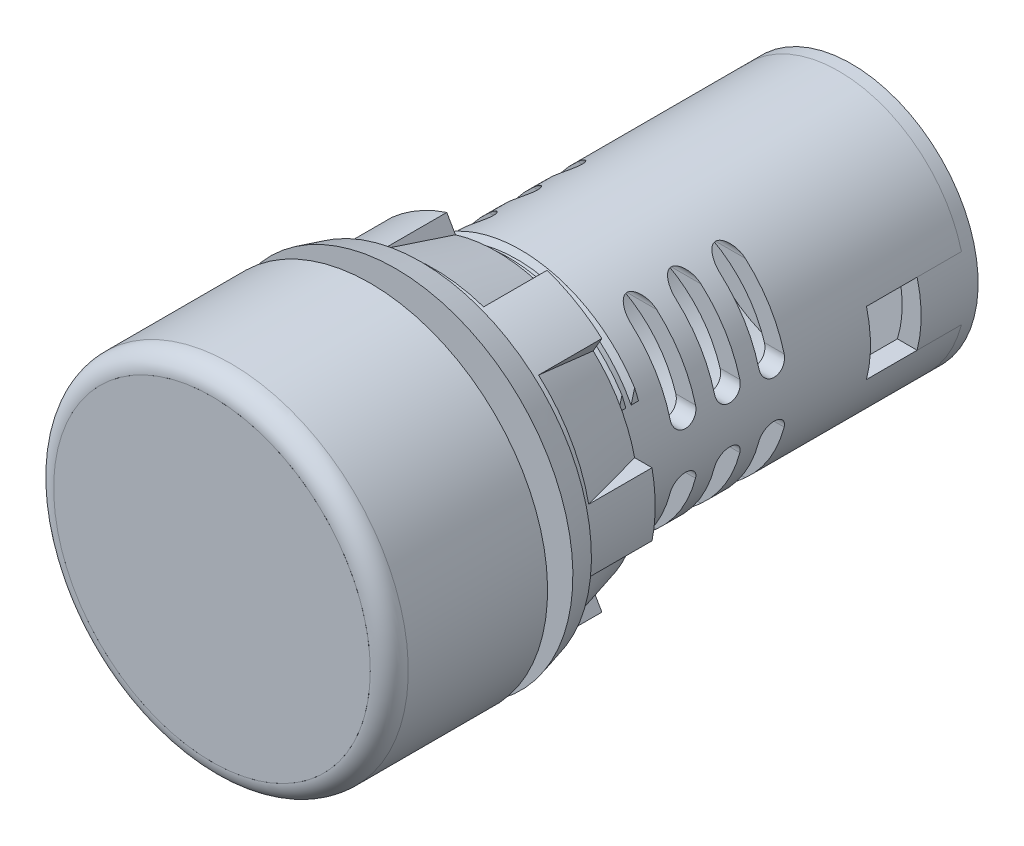
SolidWorks part; units mm, degrees
note: '?' marks a value the reader was unsure of. The reader was unsure of these and kept them because the rebuilt part matched: shared geometry of "Croquis14<4>".
material "PVC Rígido"
ref_plane "Alzado" through (0, 0, 0) normal (0, 0, 1) x (1, 0, 0)
ref_plane "Planta" through (0, 0, 0) normal (0, 1, 0) x (1, 0, 0)
ref_plane "Vista lateral" through (0, 0, 0) normal (1, 0, 0) x (0, 0, -1)
sketch "Croquis1" plane through (0, 0, 0) normal (1, 0, 0) x (0, 0, -1)
  line L0 (12.5, 10) -> (49.5, 10)
  line L2 (0, 0) -> (0, 14)
  line L3 (0, 14) -> (12.5, 14)
  line L4 (12.5, 10) -> (12.5, 14)
  line L5 (49.5, 10) -> (49.5, 0)
  line L6 (49.5, 0) -> (0, 0)
  dimension "D1" = 12.5
  dimension "D3" = 37
  dimension "D4" = 10
revolve "Revolución1" add sketch "Croquis1" angle 360 about L6
shell "Vaciado1" thickness 1.5
sketch "Croquis2" plane through (0, 0, 0) normal (1, 0, 0) x (0, 0, -1)
  line L0 (31, 10) -> (31, -10) construction
  line L1 (49.5, 10) -> (12.5, 10) construction
  line L2 (12.5, -10) -> (49.5, -10) construction
  line L3 (49.5, 0) -> (12.5, 0) construction
  line L4 (49.5, -10) -> (49.5, 10) construction
  line L5 (12.5, -10) -> (12.5, 10) construction
  line L6 (31, 7.5) -> (31, 2.5) construction
  line L7 (32, 7.5) -> (32, 2.5)
  line L8 (30, 7.5) -> (30, 2.5)
  line L9 (34.5, 7.5) -> (34.5, 2.5) construction
  line L10 (35.5, 7.5) -> (35.5, 2.5)
  line L11 (33.5, 7.5) -> (33.5, 2.5)
  line L12 (34.5, -2.5) -> (34.5, -7.5) construction
  line L13 (35.5, -2.5) -> (35.5, -7.5)
  line L14 (33.5, -2.5) -> (33.5, -7.5)
  line L16 (49.5, 2.5) -> (42, 2.5)
  line L17 (49.5, 2.5) -> (49.5, -2.5)
  line L18 (31, 7.5) -> (34.5, 7.5) construction
  line L19 (27.5, 7.5) -> (27.5, 2.5) construction
  line L20 (28.5, 7.5) -> (28.5, 2.5)
  line L21 (26.5, 7.5) -> (26.5, 2.5)
  line L22 (27.5, -2.5) -> (27.5, -7.5) construction
  line L23 (28.5, -2.5) -> (28.5, -7.5)
  line L24 (26.5, -2.5) -> (26.5, -7.5)
  line L25 (31, -2.5) -> (31, -7.5) construction
  line L26 (32, -2.5) -> (32, -7.5)
  line L27 (30, -2.5) -> (30, -7.5)
  line L28 (31, 7.5) -> (27.5, 7.5) construction
  line L29 (49.5, -2.5) -> (42, -2.5)
  line L30 (42, 2.5) -> (42, -2.5)
  line L104 (31, -2.5) -> (31, -7.5) construction
  line L105 (32, -2.5) -> (32, -7.5)
  line L106 (30, -2.5) -> (30, -7.5)
  line L107 (31, -2.5) -> (31, -7.5) construction
  line L108 (32, -2.5) -> (32, -7.5)
  line L109 (30, -2.5) -> (30, -7.5)
  arc A0 (32, 7.5) -> (30, 7.5) centre (31, 7.5) ccw
  arc A1 (30, 2.5) -> (32, 2.5) centre (31, 2.5) ccw
  arc A2 (35.5, 7.5) -> (33.5, 7.5) centre (34.5, 7.5) ccw
  arc A3 (33.5, 2.5) -> (35.5, 2.5) centre (34.5, 2.5) ccw
  arc A4 (35.5, -2.5) -> (33.5, -2.5) centre (34.5, -2.5) ccw
  arc A5 (33.5, -7.5) -> (35.5, -7.5) centre (34.5, -7.5) ccw
  arc A8 (28.5, 7.5) -> (26.5, 7.5) centre (27.5, 7.5) ccw
  arc A9 (26.5, 2.5) -> (28.5, 2.5) centre (27.5, 2.5) ccw
  arc A10 (28.5, -2.5) -> (26.5, -2.5) centre (27.5, -2.5) ccw
  arc A11 (26.5, -7.5) -> (28.5, -7.5) centre (27.5, -7.5) ccw
  arc A12 (32, -2.5) -> (30, -2.5) centre (31, -2.5) ccw
  arc A13 (30, -7.5) -> (32, -7.5) centre (31, -7.5) ccw
  arc A66 (32, -2.5) -> (30, -2.5) centre (31, -2.5) ccw
  arc A67 (30, -7.5) -> (32, -7.5) centre (31, -7.5) ccw
  point P14 (31, 5)
  point P23 (34.5, 5)
  point P30 (34.5, -5)
  point P44 (26, -5)
  point P47 (27.5, 5)
  point P54 (27.5, -5)
  point P61 (31, -5)
  point P74 (26, -5)
  point P81 (26, -5)
  point P88 (26, -5)
  point P95 (26, -5)
  point P102 (26, -5)
  point P109 (26, -5)
  point P116 (26, -5)
  point P123 (26, -5)
  point P130 (26, -5)
  point P137 (26, -5)
  point P144 (26, -5)
  point P151 (33.5, -5)
  point P158 (33.5, -5)
  point P165 (26, -5)
  point P172 (26, -5)
  point P179 (33.5, -5)
  point P186 (33.5, -5)
  point P193 (26, -5)
  point P200 (26, -5)
  point P207 (33.5, -5)
  point P214 (33.5, -5)
  point P221 (26, -5)
  point P228 (26, -5)
  point P235 (31, -5)
  point P242 (31, -5)
  point P249 (31, -5)
  dimension "D3" = 1
  dimension "D1" = 5
  dimension "D2" = 5
  dimension "D6" = 3.5
  dimension "D9" = 3.5
  dimension "D10" = 5
  dimension "D11" = 7.5
  dimension "D4" = 2
  dimension "D5" = 2
  dimension "D7" = 2
  dimension "D8" = 2
extrude "Cortar-Extruir1" cut sketch "Croquis2" against normal through all both and the other way through all
sketch "Croquis14" plane through (0, 0, -49.5) normal (0, 0, -1) x (-1, 0, 0)
  line L0 (9.6825, 2.5) -> (8.124, 2.5) construction
  line L1 (8.124, -2.5) -> (9.6825, -2.5) construction
  line L2 (-9.6825, -2.5) -> (-8.124, -2.5) construction
  line L3 (-8.124, 2.5) -> (-9.6825, 2.5) construction
  line L4 (9.6825, 2.5) -> (8.124, 2.5)
  line L5 (8.124, -2.5) -> (9.6825, -2.5)
  line L6 (-9.6825, -2.5) -> (-8.124, -2.5)
  line L7 (-8.124, 2.5) -> (-9.6825, 2.5)
  circle A0 centre (0, 0) radius 10 construction
  circle A1 centre (0, 0) radius 10
  arc A2 (9.6825, -2.5) -> (9.6825, 2.5) centre (0, 0) ccw construction
  arc A3 (8.124, -2.5) -> (8.124, 2.5) centre (0, 0) ccw construction
  arc A4 (-9.6825, 2.5) -> (-9.6825, -2.5) centre (0, 0) ccw construction
  arc A5 (-8.124, 2.5) -> (-8.124, -2.5) centre (0, 0) ccw construction
  arc A6 (9.6825, -2.5) -> (9.6825, 2.5) centre (0, 0) ccw
  arc A7 (8.124, -2.5) -> (8.124, 2.5) centre (0, 0) ccw
  arc A8 (-9.6825, 2.5) -> (-9.6825, -2.5) centre (0, 0) ccw
  arc A9 (-8.124, 2.5) -> (-8.124, -2.5) centre (0, 0) ccw
  circle A10 centre (-5, 0) radius 2.5
  circle A11 centre (5, 0) radius 2.5
  line M1 (-9.6825, 2.5) -> (9.6825, 2.5)
  arc M2 (9.6825, 2.5) -> (-9.6825, 2.5) centre (0, 0) ccw
  dimension "D1" = 5
  dimension "D2" = 5
extrude "Saliente-Extruir3" add sketch "Croquis14" along normal blind 1 separate body contours A9 A1 L6 M1 | M2 M1 | A9 L6 A1 L5 A7 M1 | A7 L5 A1 M1
extrude "Saliente-Extruir4" add sketch "Croquis14<4>" against normal blind 3.5 contours A9 A1 L6 M1 | A7 L5 A1 M1
sketch "Croquis14<4>" plane through (0, 0, -49.5) normal (0, 0, -1) x (-1, 0, 0) same geometry as "Croquis14"
ref_plane "Plano1" through (0, 0, -46.5) normal (0, 0, -1) x (-1, 0, 0)
sketch "Croquis4" plane through (0, 0, -46.5) normal (0, 0, -1) x (-1, 0, 0)
  arc A3 (8.124, -2.5) -> (8.124, 2.5) centre (0, 0) ccw construction
  arc A4 (-8.124, -2.5) -> (8.124, -2.5) centre (0, 0) ccw construction
  arc A5 (-8.124, 2.5) -> (-8.124, -2.5) centre (0, 0) ccw construction
  arc A6 (8.124, 2.5) -> (-8.124, 2.5) centre (0, 0) ccw construction
  arc A7 (8.124, -2.5) -> (8.124, 2.5) centre (0, 0) ccw
  arc A8 (-8.124, -2.5) -> (8.124, -2.5) centre (0, 0) ccw
  arc A9 (-8.124, 2.5) -> (-8.124, -2.5) centre (0, 0) ccw
  arc A10 (8.124, 2.5) -> (-8.124, 2.5) centre (0, 0) ccw
extrude "Saliente-Extruir1" add sketch "Croquis4" along normal blind 2.5
ref_plane "Plano2" through (0, 0, -24.5) normal (0, 0, -1) x (-1, 0, 0)
sketch "Croquis6" plane through (0, 0, -24.5) normal (0, 0, -1) x (-1, 0, 0)
  circle A0 centre (0, 0) radius 10
  dimension "D1" = 20
sketch "Croquis9" plane through (0, 0, 0) normal (1, 0, 0) x (0, 0, -1)
  line L0 (24.5, 10) -> (24.2113, 10.5)
  line L1 (24.5, -15.4) -> (24.5, 15.4) construction
  line L2 (49.5, 10) -> (12.5, 10) construction
  line L3 (24.2113, 10.5) -> (23.9226, 10)
  line L4 (23.9226, 10) -> (24.5, 10)
  point P6 (24.2113, 10)
  dimension "D1" = 60
  dimension "D2" = 60
  dimension "D3" = 0.5
curve "Hélice/Espiral1" pitch 1 height 12 turns 12
sweep "Barrer1" add profiles "Croquis9" path "Hélice/Espiral1"
sketch "Croquis10" plane through (0, 0, -12.5) normal (0, 0, -1) x (-1, 0, 0)
  line L0 (-14, 0) -> (14, 0) construction
  line L1 (0, 14) -> (0, -14) construction
  line L2 (-9, -6) -> (-9, -4.3589)
  line L3 (-9, 6) -> (-11, 6)
  line L4 (-11, 6) -> (-11, -6)
  line L5 (-11, -6) -> (-9, -6)
  line L6 (-9, 4.3589) -> (-9, 6)
  line L7 (9, 6) -> (11, 6)
  line L8 (11, 6) -> (11, -6)
  line L9 (11, -6) -> (9, -6)
  line L10 (9, -6) -> (9, -4.3589)
  line L11 (9, 4.3589) -> (9, 6)
  circle A0 centre (0, 0) radius 10 construction
  arc A1 (-9, 4.3589) -> (-9, -4.3589) centre (0, 0) ccw
  arc A2 (9, 4.3589) -> (9, -4.3589) centre (0, 0) cw
  circle A3 centre (0, 0) radius 14 construction
  dimension "D1" = 9
  dimension "D2" = 12
  dimension "D3" = 2
extrude "Cortar-Extruir3" cut sketch "Croquis10" along normal through all
sketch "Croquis11" plane through (0, 0, 0) normal (0, 0, 1) x (1, 0, 0)
  circle A1 centre (0, 0) radius 12.5 construction
  circle A2 centre (0, 0) radius 12.5
extrude "Saliente-Extruir2" add sketch "Croquis11" against normal blind 7.5 separate body
shell "Vaciado5" thickness 1.5
fillet "Redondeo1" radius 1.5 1 edges at (0, 14, 0)
ref_plane "Plano3" through (0, 0, -14.5) normal (0, 0, -1) x (-1, 0, 0)
sketch "Croquis15" plane through (0, 0, -14.5) normal (0, 0, -1) x (-1, 0, 0)
  circle A0 centre (0, 0) radius 10 construction
  circle A1 centre (0, 0) radius 10
  circle A2 centre (0, 0) radius 14
  dimension "D1" = 4
extrude "Saliente-Extruir6" add sketch "Croquis15" along normal blind 2 separate body
sketch "Croquis16" plane through (0, 0, -16.5) normal (0, 0, -1) x (-1, 0, 0)
  circle A0 centre (0, 0) radius 10 construction
  circle A1 centre (0, 0) radius 10
  circle A2 centre (0, 0) radius 12.5
  dimension "D1" = 2.5
extrude "Saliente-Extruir7" add sketch "Croquis16" along normal blind 6
chamfer "Chaflán1" distance 2 angle 15 1 edges at (0, 14, -16.5)
chamfer "Chaflán2" distance 5 angle 15 1 edges at (0, 12.5, -22.5)
sketch "Croquis17" plane through (0, 0, -22.5) normal (0, 0, -1) x (-1, 0, 0)
  circle A1 centre (0, 0) radius 10.5
  dimension "D1" = 21
sketch "Croquis19" plane through (0, 0, 0) normal (1, 0, 0) x (0, 0, -1)
  line L0 (22.2113, 10) -> (22.5, 10.5)
  line L1 (22.5, 10.5) -> (21.9226, 10.5)
  line L2 (21.9226, 10.5) -> (22.2113, 10)
  line L5 (22.5, -11.1603) -> (22.5, 11.1603) construction
  line L6 (22.5, 10) -> (14.5, 10) construction
  dimension "D1" = 60
  dimension "D2" = 60
  dimension "D3" = 0.5
curve "Hélice/Espiral3" pitch 1 height 9 turns 9
sketch "Croquis20" plane through (0, 0, -16.5) normal (0, 0, -1) x (-1, 0, 0)
  line L0 (-11.1603, 0) -> (-12.5, 0) construction
  line L1 (-3.9587, 11.8566) -> (-3.2733, 10.6694)
  line L2 (-12.2474, -2.5) -> (-10.8766, -2.5)
  line L3 (-8.2888, 9.3566) -> (-7.6034, 8.1694)
  line L4 (-12.2474, 2.5) -> (-10.8766, 2.5)
  line L5 (8.2888, 9.3566) -> (7.6034, 8.1694)
  line L6 (3.9587, 11.8566) -> (3.2733, 10.6694)
  line L7 (12.2474, -2.5) -> (10.8766, -2.5)
  line L8 (12.2474, 2.5) -> (10.8766, 2.5)
  line L9 (3.9587, -11.8566) -> (3.2733, -10.6694)
  line L10 (8.2888, -9.3566) -> (7.6034, -8.1694)
  line L11 (-8.2888, -9.3566) -> (-7.6034, -8.1694)
  line L12 (-3.9587, -11.8566) -> (-3.2733, -10.6694)
  circle A0 centre (0, 0) radius 11.1603 construction
  circle A1 centre (0, 0) radius 12.5 construction
  arc A2 (-10.8766, 2.5) -> (-10.8766, -2.5) centre (0, 0) ccw
  arc A3 (-3.2733, 10.6694) -> (-7.6034, 8.1694) centre (0, 0) ccw
  arc A4 (-3.9587, 11.8566) -> (-8.2888, 9.3566) centre (0, 0) ccw
  arc A5 (7.6034, 8.1694) -> (3.2733, 10.6694) centre (0, 0) ccw
  arc A6 (8.2888, 9.3566) -> (3.9587, 11.8566) centre (0, 0) ccw
  arc A7 (10.8766, -2.5) -> (10.8766, 2.5) centre (0, 0) ccw
  arc A9 (12.2474, -2.5) -> (12.2474, 2.5) centre (0, 0) ccw
  arc A10 (-12.2474, 2.5) -> (-12.2474, -2.5) centre (0, 0) ccw
  arc A11 (3.2733, -10.6694) -> (7.6034, -8.1694) centre (0, 0) ccw
  arc A12 (3.9587, -11.8566) -> (8.2888, -9.3566) centre (0, 0) ccw
  arc A13 (-7.6034, -8.1694) -> (-3.2733, -10.6694) centre (0, 0) ccw
  arc A14 (-8.2888, -9.3566) -> (-3.9587, -11.8566) centre (0, 0) ccw
  point P7 (-11.8301, 0)
  point P32 (0, 0)
  dimension "D1" = 5
  dimension "D3" = 2.5
extrude "Saliente-Extruir9" add sketch "Croquis20" along normal blind 6
sketch "Croquis21" plane through (0, 0, -50.5) normal (0, 0, -1) x (-1, 0, 0)
  point P0 (-5, 0)
  point P1 (5, 0)
sketch "2_1_Point" plane through (0, 0, -50.5) normal (0, 0, -1) x (-1, 0, 0)
  point P0 (-5, 0)
other "2_1" parameters "Diámetro"=2, "Longitud de terminal"=2
ref_axis "Eje1" through (5, 0, -60.5) along (0, 0, 1)?
sketch "2_2_Point" plane through (0, 0, -50.5) normal (0, 0, -1) x (-1, 0, 0)
  point P0 (5, 0)
other "2_2" parameters "Diámetro"=2, "Longitud de terminal"=2
ref_axis "Eje2" through (-5, 0, -60.5) along (0, 0, 1)?
equation "\"D2@Croquis14\"=\"D1@Croquis14\""
